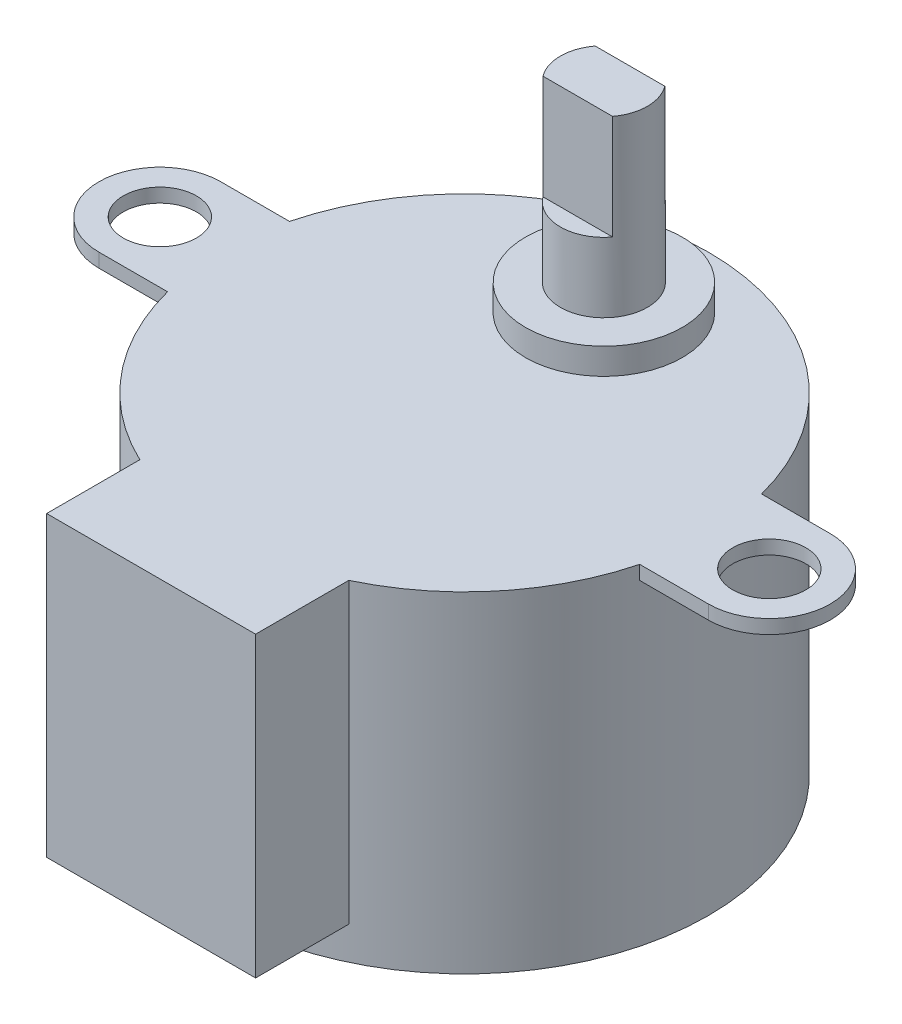
SolidWorks part; units mm, degrees
ref_plane "Alzado" through (0, 0, 0) normal (0, 0, 1) x (1, 0, 0)
ref_plane "Planta" through (0, 0, 0) normal (0, 1, 0) x (1, 0, 0)
ref_plane "Vista lateral" through (0, 0, 0) normal (1, 0, 0) x (0, 0, -1)
sketch "Croquis1" plane through (0, 0, 0) normal (0, 1, 0) x (1, 0, 0)
  circle A0 centre (0, 0) radius 14
  dimension "D1" = 28
extrude "Saliente-Extruir1" add sketch "Croquis1" along normal blind 19
sketch "Croquis2" plane through (0, 19, 0) normal (0, 1, 0) x (1, 0, 0)
  line L0 (-17.5, 3.5) -> (-13.5554, 3.5)
  line L1 (-17.5, -3.5) -> (-13.5554, -3.5)
  line L2 (17.5, -3.5) -> (13.5554, -3.5)
  line L3 (17.5, 3.5) -> (13.5554, 3.5)
  circle A0 centre (-17.5, 0) radius 2.1
  circle A1 centre (17.5, 0) radius 2.1
  arc A2 (-17.5, 3.5) -> (-17.5, -3.5) centre (-17.5, 0) ccw
  arc A3 (17.5, -3.5) -> (17.5, 3.5) centre (17.5, 0) ccw
  circle A4 centre (0, 0) radius 14 construction
  arc A5 (-13.5554, -3.5) -> (13.5554, -3.5) centre (0, 0) ccw
  arc A6 (13.5554, 3.5) -> (-13.5554, 3.5) centre (0, 0) ccw
  dimension "D1" = 7
  dimension "D2" = 4.2
  dimension "D3" = 4.2
  dimension "D4" = 7
  dimension "D5" = 35
  dimension "D6" = 17.5
extrude "Saliente-Extruir2" add sketch "Croquis2" against normal blind 0.8
sketch "Croquis3" plane through (0, 0, 0) normal (0, 0, 1) x (1, 0, 0)
  line L0 (13.5554, 19) -> (-13.5554, 19) construction
  line L1 (-6, 19) -> (6, 19)
  line L2 (-6, 19) -> (-6, 1.9)
  line L3 (-6, 1.9) -> (6, 1.9)
  line L4 (6, 19) -> (6, 1.9)
  line L5 (-14, 0) -> (14, 0) construction
  point P6 (0, 19)
  dimension "D1" = 12
  dimension "D2" = 1.9
extrude "Saliente-Extruir3" add sketch "Croquis3" against normal up to surface (5.3509 mm away) from offset 18 up to face at (0, 18.6, 0)
sketch "Croquis4" plane through (0, 19, 0) normal (0, 1, 0) x (1, 0, 0)
  circle A0 centre (0, 8) radius 4.5
  dimension "D1" = 9
  dimension "D2" = 8
extrude "Saliente-Extruir4" add sketch "Croquis4" along normal blind 1.5
sketch "Croquis5" plane through (0, 20.5, 0) normal (0, 1, 0) x (1, 0, 0)
  circle A0 centre (0, 8) radius 2.5
  circle A1 centre (0, 8) radius 4.5 construction
  dimension "D1" = 5
extrude "Saliente-Extruir5" add sketch "Croquis5" along normal blind 10
sketch "Croquis7" plane through (0, 30.5, 0) normal (0, 1, 0) x (1, 0, 0)
  line L0 (-2.5, 8) -> (2.5, 8) construction
  line L2 (3.3151, 9.5) -> (-3.2429, 9.5)
  line L3 (3.3151, 9.5) -> (3.3151, 10.8684)
  line L4 (3.3151, 10.8684) -> (-3.2429, 10.8684)
  line L5 (-3.2429, 9.5) -> (-3.2429, 10.8684)
  line L6 (3.1602, 4.5119) -> (-3.2429, 4.5119)
  line L7 (3.1602, 4.5119) -> (3.1602, 6.5)
  line L8 (3.1602, 6.5) -> (-3.2429, 6.5)
  line L9 (-3.2429, 4.5119) -> (-3.2429, 6.5)
  circle A0 centre (0, 8) radius 2.5 construction
  circle A1 centre (0, 8) radius 2.5 construction
  dimension "D1" = 1.5
  dimension "D2" = 1.5
extrude "Cortar-Extruir1" cut sketch "Croquis7" against normal blind 6
